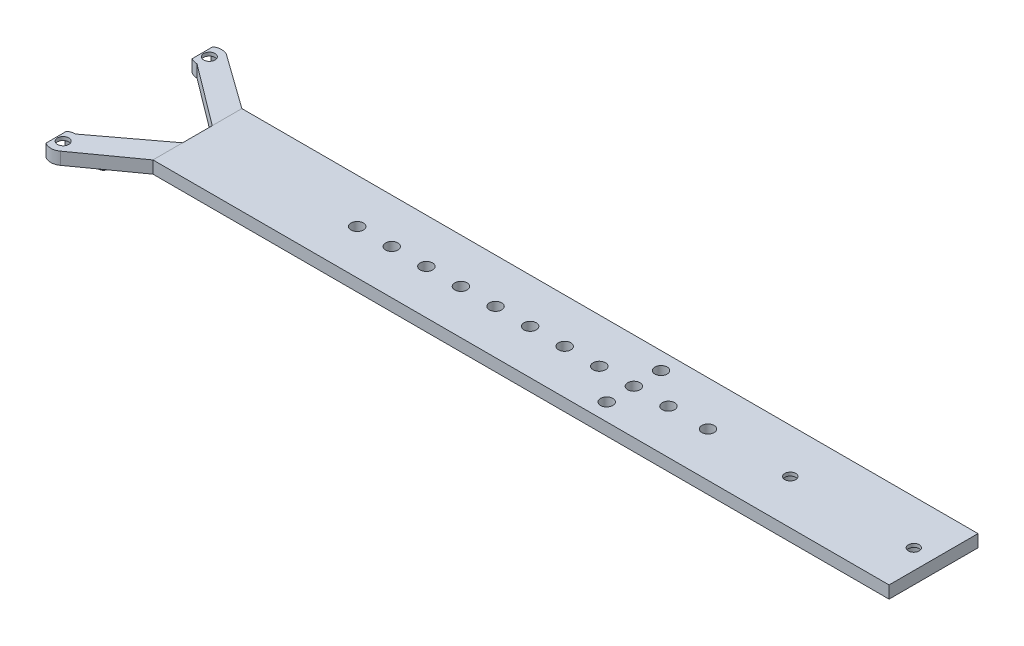
SolidWorks part; units mm, degrees
ref_plane "Płaszczyzna przednia" through (0, 0, 0) normal (0, 0, 1) x (1, 0, 0)
ref_plane "Płaszczyzna górna" through (0, 0, 0) normal (0, 1, 0) x (1, 0, 0)
ref_plane "Płaszczyzna prawa" through (0, 0, 0) normal (1, 0, 0) x (0, 0, -1)
sketch "Szkic1" plane through (0, -0.6011, 0) normal (0, -1, 0) x (1, 0, 0)
  line L11 (-159.9499, 53.1337) -> (-159.9499, 35.1337)
  line L14 (-10.9498, 35.1337) -> (-159.9499, 35.1337)
  line L15 (-10.9498, 35.1337) -> (-10.9498, 53.1337)
  line L16 (-10.9498, 53.1337) -> (-159.9499, 53.1337)
  circle A0 centre (-14.9498, 44.1337) radius 1.1 construction
  circle A1 centre (-39.9499, 44.1337) radius 1.1 construction
  circle A2 centre (-14.9498, 44.1337) radius 1.1
  circle A3 centre (-39.9499, 44.1337) radius 1.1
  dimension "D1" = 18
  dimension "D2" = 9
  dimension "D3" = 9
  dimension "D4" = 4
  dimension "D5" = 120
extrude "Dodanie-wyciągnięcie1" add sketch "Szkic1" along normal blind 2.5
sketch "Szkic3" plane through (0, -3.1011, 0) normal (0, -1, 0) x (1, 0, 0)
  line L0 (-169.9482, 58.1605) -> (-170.1612, 57.6835) construction
  line L1 (-169.9482, 28.5605) -> (-170.1612, 28.0835) construction
  line L2 (-169.9482, 58.1605) -> (-170.1612, 57.6835)
  line L3 (-169.9482, 28.5605) -> (-170.1612, 28.0835)
  line L4 (-172.326, 56.4332) -> (-159.9499, 47.1337)
  line L5 (-159.9499, 53.1337) -> (-159.9499, 35.1337) construction
  line L6 (-170.8688, 60.9652) -> (-159.9499, 53.1337)
  line L7 (-159.9499, 53.1337) -> (-159.9499, 47.1337)
  line L8 (-172.326, 31.8338) -> (-159.9499, 41.1337)
  line L9 (-170.8687, 27.3018) -> (-159.9499, 35.1337)
  circle A0 centre (-172.326, 29.3335) radius 1.15 construction
  circle A1 centre (-172.326, 58.9335) radius 1.15 construction
  circle A2 centre (-172.326, 29.3335) radius 1.15
  circle A3 centre (-172.326, 58.9335) radius 1.15
  circle A4 centre (-172.326, 29.3335) radius 2.5003
  circle A5 centre (-172.326, 58.9335) radius 2.5003
  point P24 (-170.8553, 60.9644)
  line M3 (-159.9499, 53.1337) -> (-159.9499, 35.1337)
  dimension "D1" = 6
  dimension "D2" = 6
extrude "Dodanie-wyciągnięcie2" add sketch "Szkic3" against normal blind 2.5 separate body contours A4 L9 L8 M3 | A5 L4 L6 M3 | A5 A3 | A4 A2 region at (-165.2039, -3.1011, 53.9008) region at (-165.2039, -3.1011, 34.3663) region at (-174.639, -3.1011, 59.6772) region at (-170.6081, -3.1011, 31.0515)
sketch "Szkic4" plane through (0, -3.1011, 0) normal (0, -1, 0) x (1, 0, 0)
  line L0 (-173.7263, 27.2621) -> (-173.7263, 31.4049)
  line L1 (-173.7263, 56.862) -> (-173.7263, 61.0049)
  arc A0 (-172.326, 31.8338) -> (-170.8687, 27.3018) centre (-172.326, 29.3335) ccw construction
  arc A1 (-170.8688, 60.9652) -> (-172.326, 56.4332) centre (-172.326, 58.9335) ccw construction
  arc A2 (-173.7263, 61.0049) -> (-173.7263, 56.862) centre (-172.326, 58.9335) ccw
  arc A3 (-173.7263, 31.4049) -> (-173.7263, 27.2621) centre (-172.326, 29.3335) ccw
extrude "Wytnij-wyciągnięcie1" cut sketch "Szkic4" against normal up to next (2.5 mm away)
sketch "Szkic5" plane through (0, -3.1011, 0) normal (0, -1, 0) x (-1, 0, 0)
  line L0 (172.326, -56.4332) -> (159.9499, -47.1337) construction
  line L3 (168.9499, -55.6461) -> (165.9499, -55.6461)
  arc A1 (165.9499, -55.6461) -> (168.9499, -55.6461) centre (167.4499, -55.6461) ccw
  dimension "D1" = 3
  dimension "D2" = 2.3
revolve "Obrót2" add sketch "Szkic5" angle 360 about L3
sketch "Szkic6" plane through (0, -3.1011, 0) normal (0, -1, 0) x (1, 0, 0)
  line L0 (-170.8687, 27.3018) -> (-159.9499, 35.1337) construction
  line L1 (-168.9499, 32.5846) -> (-165.9499, 32.5846)
  arc A0 (-165.9499, 32.5846) -> (-168.9499, 32.5846) centre (-167.4499, 32.5846) ccw
  circle A1 centre (-167.4499, 55.6461) radius 1.5 construction
  dimension "D1" = 2.3
revolve "Obrót3" add sketch "Szkic6" angle 360 about L1
sketch "Szkic7" plane through (0, -3.1011, 0) normal (0, -1, 0) x (1, 0, 0)
  line L0 (-159.9499, 35.1337) -> (-10.9498, 35.1337) construction
  circle A0 centre (-39.9499, 44.1337) radius 2.25
  circle A1 centre (-14.9498, 44.1337) radius 2.25
  circle A2 centre (-172.326, 58.9335) radius 2.25
  circle A3 centre (-172.326, 29.3335) radius 2.25
  circle A4 centre (-56.6073, 44.1337) radius 1.25
  circle A5 centre (-64.6073, 44.1337) radius 1.25
  circle A6 centre (-71.6073, 44.1337) radius 1.25
  circle A7 centre (-78.6073, 44.1337) radius 1.25
  circle A8 centre (-85.6073, 44.1337) radius 1.25
  circle A9 centre (-92.6073, 44.1337) radius 1.25
  circle A10 centre (-99.6073, 44.1337) radius 1.25
  circle A11 centre (-106.6073, 44.1337) radius 1.25
  circle A12 centre (-113.6073, 44.1337) radius 1.25
  circle A13 centre (-120.6073, 44.1337) radius 1.25
  circle A14 centre (-127.6073, 44.1337) radius 1.25
  point P34 (-74.5546, 44.1337)
  point P35 (0, 0)
  point P36 (0, 0)
  point P37 (0, 0)
  point P38 (-52.94, 45.3527)
  point P41 (-56.6073, 44.1337)
  dimension "D1" = 4.5
  dimension "D2" = 4.5
  dimension "D3" = 4.5
  dimension "D4" = 2.5
  dimension "D5" = 8
  dimension "D6" = 7
  dimension "D7" = 7
  dimension "D8" = 7
  dimension "D9" = 7
  dimension "D10" = 7
  dimension "D11" = 7
  dimension "D12" = 7
  dimension "D13" = 7
  dimension "D14" = 7
  dimension "D15" = 9
extrude "Wytnij-wyciągnięcie2" cut sketch "Szkic7" against normal blind 1.8
sketch "Szkic8" plane through (0, -3.1011, 0) normal (0, -1, 0) x (1, 0, 0)
  circle A0 centre (-56.6073, 44.1337) radius 1.25 construction
  circle A1 centre (-64.6073, 44.1337) radius 1.25 construction
  circle A2 centre (-71.6073, 44.1337) radius 1.25 construction
  circle A3 centre (-78.6073, 44.1337) radius 1.25 construction
  circle A4 centre (-85.6073, 44.1337) radius 1.25 construction
  circle A5 centre (-92.6073, 44.1337) radius 1.25 construction
  circle A6 centre (-99.6073, 44.1337) radius 1.25 construction
  circle A7 centre (-106.6073, 44.1337) radius 1.25 construction
  circle A8 centre (-113.6073, 44.1337) radius 1.25 construction
  circle A9 centre (-120.6073, 44.1337) radius 1.25 construction
  circle A10 centre (-127.6073, 44.1337) radius 1.25 construction
  circle A11 centre (-56.6073, 44.1337) radius 1.25
  circle A12 centre (-64.6073, 44.1337) radius 1.25
  circle A13 centre (-71.6073, 44.1337) radius 1.25
  circle A14 centre (-78.6073, 44.1337) radius 1.25
  circle A15 centre (-85.6073, 44.1337) radius 1.25
  circle A16 centre (-92.6073, 44.1337) radius 1.25
  circle A17 centre (-99.6073, 44.1337) radius 1.25
  circle A18 centre (-106.6073, 44.1337) radius 1.25
  circle A19 centre (-113.6073, 44.1337) radius 1.25
  circle A20 centre (-120.6073, 44.1337) radius 1.25
  circle A21 centre (-127.6073, 44.1337) radius 1.25
extrude "Wytnij-wyciągnięcie3" cut sketch "Szkic8" against normal through all
sketch "Szkic9" plane through (0, -0.6011, 0) normal (0, 1, 0) x (1, 0, 0)
  line L0 (-10.9498, -53.1337) -> (-159.9499, -53.1337) construction
  line L1 (-159.9499, -35.1337) -> (-10.9498, -35.1337) construction
  circle A0 centre (-71.6073, -49.6337) radius 1.25
  circle A1 centre (-71.6073, -38.6337) radius 1.25
  point P8 (-71.6073, -38.6337)
  point P9 (0, 0)
  dimension "D1" = 2.5
  dimension "D2" = 2.5
  dimension "D3" = 3.5
  dimension "D4" = 3.5
extrude "Wytnij-wyciągnięcie4" cut sketch "Szkic9" against normal through all
